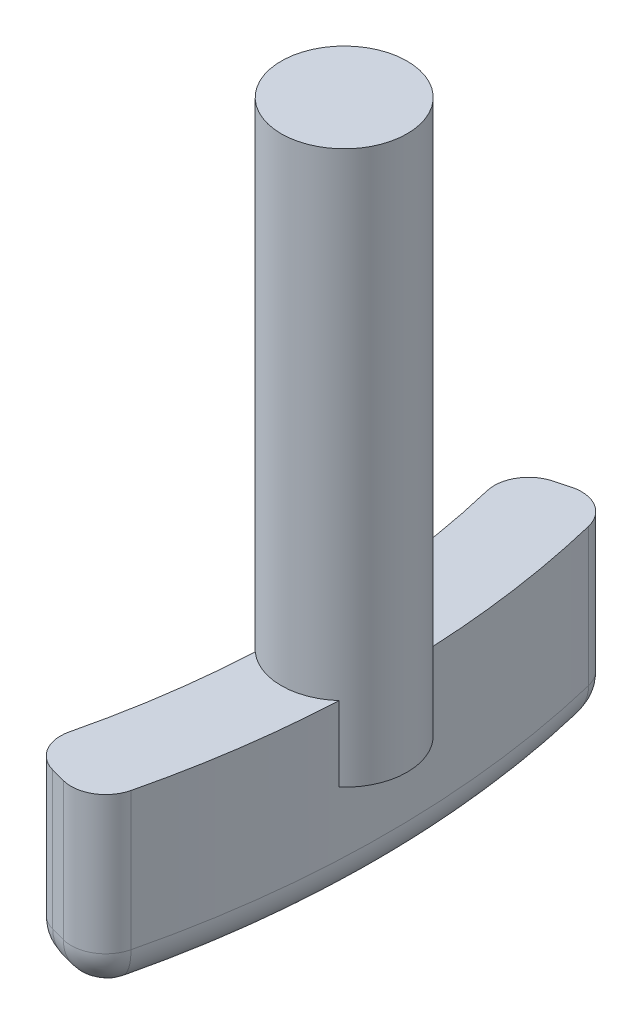
SolidWorks part; units mm, degrees
material "ABS"
ref_plane "Front Plane" through (0, 0, 0) normal (0, 0, 1) x (1, 0, 0)
ref_plane "Top Plane" through (0, 0, 0) normal (0, 1, 0) x (1, 0, 0)
ref_plane "Right Plane" through (0, 0, 0) normal (1, 0, 0) x (0, 0, -1)
sketch "Эскиз1" plane through (0, 0, 0) normal (0, 1, 0) x (1, 0, 0)
  line L10 (-0.9455, -8.3427) -> (-0.4624, -8.4721)
  line L11 (-0.9455, 8.3427) -> (-0.4624, 8.4721)
  arc A30 (-0.4624, -8.4721) -> (0.9529, -7.6322) centre (-0.1648, -7.3613) ccw
  arc A31 (0.9529, 7.6322) -> (0.9529, -7.6322) centre (-30.5354, 0) cw
  arc A32 (0.9529, 7.6322) -> (-0.4624, 8.4721) centre (-0.1648, 7.3613) ccw
  arc A33 (-0.9455, 8.3427) -> (-1.7656, 6.9614) centre (-0.6479, 7.2319) ccw
  arc A34 (-1.7656, 6.9614) -> (-1.7656, -6.9614) centre (-30.5354, 0) cw
  arc A35 (-0.9455, -8.3427) -> (-1.7656, -6.9614) centre (-0.6479, -7.2319) cw
  point P13 (0.3409, 8.2822)
  point P14 (0.3409, -8.2822)
extrude "Бобышка-Вытянуть1" add sketch "Эскиз1" along normal blind 5
ref_plane "Плоскость1" through (0, 2.5, 0) normal (0, 1, 0) x (1, 0, 0)
sketch "Эскиз2" plane through (0, 2.5, 0) normal (0, 1, 0) x (1, 0, 0)
  circle A2 centre (0.4313, 0) radius 2.1
  dimension "D1" = 4.2
extrude "Бобышка-Вытянуть2" add sketch "Эскиз2" along normal blind 18.44
sketch "Эскиз3" plane through (0, 0, 0) normal (0, -1, 0) x (1, 0, 0)
  line L0 (-0.4624, -8.4721) -> (-0.9455, -8.3427)
  line L1 (-0.9455, 8.3427) -> (-0.4624, 8.4721)
  arc A0 (-1.7656, -6.9614) -> (-0.9455, -8.3427) centre (-0.6479, -7.2319) ccw
  arc A1 (-1.7656, -6.9614) -> (-1.7656, 6.9614) centre (-30.5354, 0) ccw
  arc A2 (-0.9455, 8.3427) -> (-1.7656, 6.9614) centre (-0.6479, 7.2319) ccw
  arc A3 (0.9529, 7.6322) -> (-0.4624, 8.4721) centre (-0.1648, 7.3613) ccw
  arc A4 (0.9529, -7.6322) -> (0.9529, 7.6322) centre (-30.5354, 0) ccw
  arc A5 (-0.4624, -8.4721) -> (0.9529, -7.6322) centre (-0.1648, -7.3613) ccw
extrude "Бобышка-Вытянуть3" add sketch "Эскиз3" along normal blind 1
fillet "Скругление1" radius 1.4 8 edges at (0.4221, -1, -8.3503) (-0.704, -1, -8.4074) (-1.6367, -1, -7.819) (-0.9354, -1, 0) (-1.6367, -1, 7.819) (-0.704, -1, 8.4074) (0.4221, -1, 8.3503) (1.8646, -1, 0)
